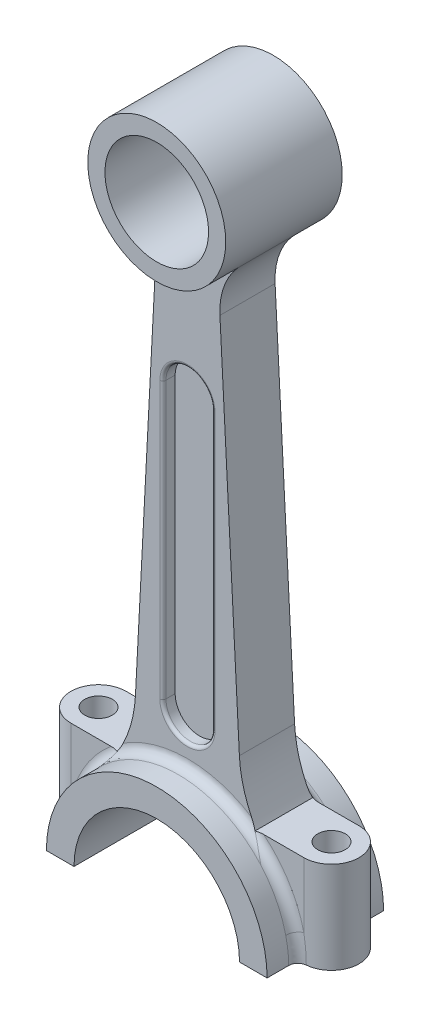
SolidWorks part; units mm, degrees
ref_plane "Front Plane" through (0, 0, 0) normal (0, 0, 1) x (1, 0, 0)
ref_plane "Top Plane" through (0, 0, 0) normal (0, 1, 0) x (1, 0, 0)
ref_plane "Right Plane" through (0, 0, 0) normal (1, 0, 0) x (0, 0, -1)
sketch "Sketch2" plane through (0, 0, 0) normal (0, 0, 1) x (1, 0, 0)
  line L0 (-18.8406, 134.9756) -> (-26.6903, -14.8055)
  line L1 (1.1594, 134.9756) -> (9.0091, -14.8055)
  line L2 (-8.8406, 155.1312) -> (-8.8406, -46.0688) construction
  line L3 (-44.8406, -46.0688) -> (-35.8406, -46.0688)
  line L4 (18.1594, -46.0688) -> (27.1594, -46.0688)
  circle A0 centre (-8.8406, 155.1312) radius 16.9
  circle A1 centre (-8.8406, 155.1312) radius 22.5
  arc A2 (18.1594, -46.0688) -> (-35.8406, -46.0688) centre (-8.8406, -46.0688) ccw
  arc A3 (27.1594, -46.0688) -> (-44.8406, -46.0688) centre (-8.8406, -46.0688) ccw
  arc A4 (-18.8406, 134.9756) -> (1.1594, 134.9756) centre (-8.8406, 155.1312) ccw
  arc A5 (-18.8406, 134.9756) -> (11.227, 144.9557) centre (-8.8406, 155.1312) ccw
  arc A6 (9.0091, -14.8055) -> (-26.6903, -14.8055) centre (-8.8406, -46.0688) ccw
  dimension "D1" = 45
  dimension "D2" = 33.8
  dimension "D3" = 72
  dimension "D4" = 54
  dimension "D5" = 201.2
  dimension "D6" = 6
  dimension "D7" = 3
  dimension "D8" = 20
extrude "Boss-Extrude1" add sketch "Sketch2" along normal mid plane 38 contours A2 | A3 | A0 | A1
extrude "Boss-Extrude2" add sketch "Sketch2<12>" along normal mid plane 18 contours A1 | L0 A6 L1 A4
sketch "Sketch2<12>" plane through (0, 0, 0) normal (0, 0, 1) x (1, 0, 0) same geometry as "Sketch2"
extrude "Cut-Extrude1" cut sketch "Sketch2<13>" against normal through all both and the other way through all contours A0
sketch "Sketch2<13>" plane through (0, 0, 0) normal (0, 0, 1) x (1, 0, 0) same geometry as "Sketch2"
sketch "Sketch3" plane through (0, 0, 9) normal (0, 0, 1) x (1, 0, 0)
  line L0 (-8.8406, 155.1312) -> (-8.8406, -46.0688) construction
  line L1 (-8.8406, 5.2856) -> (-8.8406, 95.2856) construction
  line L2 (-16.8406, 5.2856) -> (-16.8406, 95.2856)
  line L3 (-0.8406, 5.2856) -> (-0.8406, 95.2856)
  arc A0 (-16.8406, 5.2856) -> (-0.8406, 5.2856) centre (-8.8406, 5.2856) ccw
  arc A1 (-0.8406, 95.2856) -> (-16.8406, 95.2856) centre (-8.8406, 95.2856) ccw
  point P6 (-8.8406, 50.2856)
  dimension "D2" = 8
  dimension "D1" = 90
extrude "Cut-Extrude2" cut sketch "Sketch3" against normal blind 4 and the other way through all contours L3 A1 L2 A0
mirror "Mirror1" about plane through (0, 0, 0) normal (0, 0, 1) of "Cut-Extrude2"
fillet "Fillet1" radius 1 8 edges at (-16.8406, 50.2856, 9) (-8.8406, -2.7144, 9) (-0.8406, 50.2856, 9) (-8.8406, -2.7144, -9) (-0.8406, 50.2856, -9) (-8.8406, 103.2856, -9) (-8.8406, 103.2856, 9) (-16.8406, 50.2856, -9)
extrude "Boss-Extrude3" add sketch "Sketch2<14>" along normal mid plane 38 contours A3 L3 A2 L4
sketch "Sketch2<14>" plane through (0, 0, 0) normal (0, 0, 1) x (1, 0, 0) same geometry as "Sketch2"
fillet "Fillet2" radius 22.5 2 edges at (1.1594, 134.9756, 0) (-18.8406, 134.9756, 0)
fillet "Fillet3" radius 40 2 edges at (-26.6903, -14.8055, 0) (9.0091, -14.8055, 0)
ref_plane "Plane1" through (0, -16.0688, 0) normal (0, -1, 0) x (-1, 0, 0)
fillet "Fillet4" radius 3 2 edges at (-8.8406, -10.0688, -9) (-8.8406, -10.0688, 9)
sketch "Sketch4" plane through (0, -16.0688, 0) normal (0, -1, 0) x (-1, 0, 0)
  line L0 (-29.1594, 0) -> (46.8406, 0) construction
  line L1 (-29.1594, 9) -> (46.8406, 9)
  line L2 (-29.1594, -9) -> (46.8406, -9)
  line L3 (35.8406, 19) -> (-18.1594, 19) construction
  arc A0 (-29.1594, 9) -> (-29.1594, -9) centre (-29.1594, 0) ccw
  arc A1 (46.8406, -9) -> (46.8406, 9) centre (46.8406, 0) ccw
  point P3 (8.8406, 0)
  point P10 (8.8406, 19)
  dimension "D2" = 9
  dimension "D1" = 76
extrude "Boss-Extrude5" add sketch "Sketch4" along normal up to vertex (30 mm away) up to point (27.1594, -46.0688, 19)
sketch "Sketch8" plane through (0, 0, -9) normal (0, 0, -1) x (-1, 0, 0)
  line L0 (35.8406, -46.0688) -> (-18.1594, -46.0688) construction
  line L1 (35.8406, -46.0688) -> (-18.1594, -46.0688)
  arc A0 (35.8406, -46.0688) -> (-18.1594, -46.0688) centre (8.8406, -46.0688) ccw construction
  arc A1 (35.8406, -46.0688) -> (-18.1594, -46.0688) centre (8.8406, -46.0688) ccw
extrude "Cut-Extrude3" cut sketch "Sketch8" against normal through all both and the other way through all contours L1 A1
sketch "Sketch11" plane through (0, -16.0688, 0) normal (0, -1, 0) x (-1, 0, 0)
  circle A0 centre (-29.1594, 0) radius 4.5
  circle A1 centre (46.8406, 0) radius 4.5
  dimension "D1" = 9
  dimension "D2" = 9
extrude "Cut-Extrude4" cut sketch "Sketch11" along normal through all both and the other way through all
fillet "Fillet5" radius 3 4 edges at (-42.5032, -33.3083, 9) (-42.5032, -33.3083, -9) (24.822, -33.3083, -9) (24.822, -33.3083, 9)
